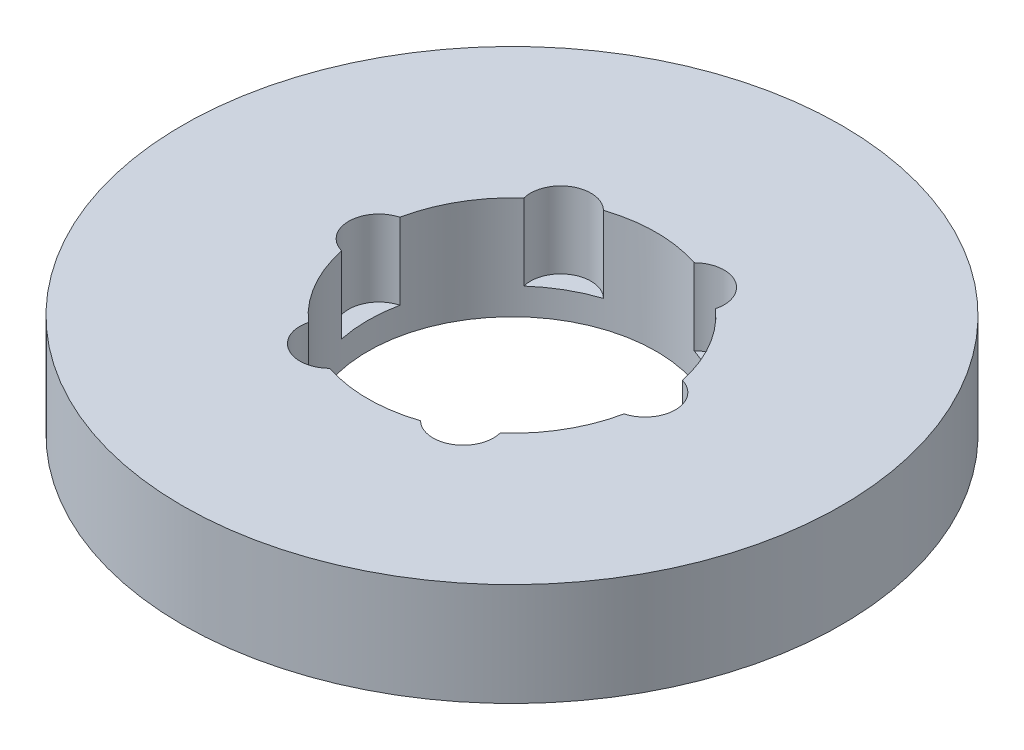
SolidWorks part; units mm, degrees
ref_plane "Front Plane" through (0, 0, 0) normal (0, 0, 1) x (1, 0, 0)
ref_plane "Top Plane" through (0, 0, 0) normal (0, 1, 0) x (1, 0, 0)
ref_plane "Right Plane" through (0, 0, 0) normal (1, 0, 0) x (0, 0, -1)
sketch "Sketch1" plane through (0, 0, 0) normal (0, 1, 0) x (1, 0, 0)
  circle A0 centre (0, 0) radius 80
  dimension "FLANGE_OD" = 160
extrude "Boss-Extrude1" add sketch "Sketch1" along normal blind 25
sketch "Sketch2" plane through (0, 0, 0) normal (0, 1, 0) x (1, 0, 0)
  circle A0 centre (0, 0) radius 35
  dimension "BORE_D" = 70
extrude "Cut-Extrude1" cut sketch "Sketch2" along normal through all
sketch "Sketch3" plane through (0, 25, 0) normal (0, 1, 0) x (1, 0, 0)
  circle A0 centre (0, 0) radius 32.3138 construction
  circle A1 centre (-32.3138, 0) radius 7.3411
  dimension "BOLT_D" = 14.6823
  dimension "BOLT_PCD" = 64.6277
extrude "Cut-Extrude2" cut sketch "Sketch3" against normal blind 18.5065
pattern_circular "CirPattern1" count 6 over 360 about axis through (0, 0, 0) along (0, 1, 0) of "Cut-Extrude2"
